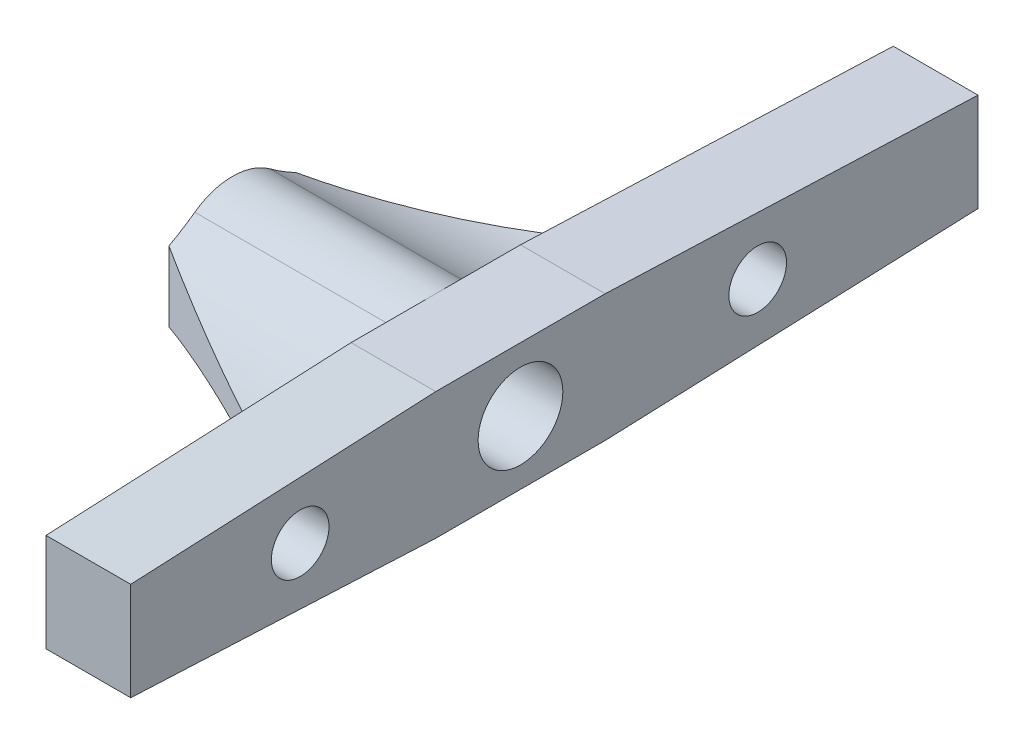
SolidWorks part; units mm, degrees
ref_plane "Front Plane" through (0, 0, 0) normal (0, 0, 1) x (1, 0, 0)
ref_plane "Top Plane" through (0, 0, 0) normal (0, 1, 0) x (1, 0, 0)
ref_plane "Right Plane" through (0, 0, 0) normal (1, 0, 0) x (0, 0, -1)
sketch "Sketch1" plane through (0, 0, 0) normal (1, 0, 0) x (0, 0, -1)
  line L1 (27, -3.75) -> (-23, -3.75)
  line L2 (27, -3.75) -> (27, 3.75)
  line L3 (27, 3.75) -> (-23, 3.75)
  line L4 (-23, -3.75) -> (-23, 3.75)
  line L5 (27, -3.75) -> (-23, 3.75) construction
  line L6 (27, 3.75) -> (-23, -3.75) construction
  circle A0 centre (0, 0) radius 2.5
  point P3 (2, 0)
  dimension "D1" = 5
  dimension "D2" = 7.5
  dimension "D3" = 50
  dimension "D4" = 2
extrude "Boss-Extrude1" add sketch "Sketch1" along normal blind 5
sketch "Sketch2" plane through (0, 0, 0) normal (-1, 0, 0) x (0, 0, 1)
  circle A0 centre (0, 0) radius 3.75
  circle A1 centre (0, 0) radius 2.5
  circle A2 centre (0, 0) radius 2.5 construction
  dimension "D1" = 7.5
extrude "Boss-Extrude2" add sketch "Sketch2" along normal blind 12
sketch "Sketch3" plane through (0, 0, 0) normal (0, 1, 0) x (1, 0, 0)
  line L1 (-12, 3.75) -> (-12, -3.75) construction
  line L2 (0, -4.125) -> (0, 4.125) construction
  line L4 (-12, 3.75) -> (0, 11.15)
  line L5 (0, 11.15) -> (0, 3.15)
  line L6 (0, 3.15) -> (-12, 3.15)
  line L7 (-12, 3.15) -> (-12, 3.75)
  line L12 (-12, -3.15) -> (0, -3.15)
  line L13 (0, -3.15) -> (0, -10.15)
  line L14 (0, -10.15) -> (-12, -3.75)
  line L15 (-12, -3.75) -> (-12, -3.15)
  dimension "D1" = 0.6
  dimension "D2" = 8
  dimension "D3" = 0.6
  dimension "D4" = 7
extrude "Boss-Extrude3" add sketch "Sketch3" along normal blind 0.7 and the other way blind 0.7
chamfer "Chamfer1" [suppressed] distance 18 angle 4
chamfer "Chamfer2" [suppressed] distance 22 angle 4
chamfer "Chamfer3" [suppressed] distance 18 angle 4
chamfer "Chamfer4" [suppressed] distance 22 angle 4
sketch "Sketch4" plane through (0, 0, 0) normal (-1, 0, 0) x (0, 0, 1)
  line L0 (2.75, 0) -> (-2.75, 0) construction
  line L1 (-12.5566, 2.5) -> (-15.4434, 2.5)
  line L2 (-15.4434, 2.5) -> (-16.8868, 0)
  line L3 (-16.8868, 0) -> (-15.4434, -2.5)
  line L4 (-15.4434, -2.5) -> (-12.5566, -2.5)
  line L5 (-12.5566, -2.5) -> (-11.1132, 0)
  line L6 (-11.1132, 0) -> (-12.5566, 2.5)
  line L7 (0, -2.75) -> (0, 2.75) construction
  line L8 (14.4434, 2.5) -> (11.5566, 2.5)
  line L9 (11.5566, 2.5) -> (10.1132, 0)
  line L10 (10.1132, 0) -> (11.5566, -2.5)
  line L11 (11.5566, -2.5) -> (14.4434, -2.5)
  line L12 (14.4434, -2.5) -> (15.8868, 0)
  line L13 (15.8868, 0) -> (14.4434, 2.5)
  circle A0 centre (-14, 0) radius 2.5 construction
  circle A1 centre (13, 0) radius 2.5 construction
  dimension "D1" = 5
  dimension "D2" = 14
  dimension "D3" = 13
extrude "Cut-Extrude1" cut sketch "Sketch4" against normal blind 2
hole_wizard "M3 Clearance Hole1" positions "Sketch6" profile "Sketch7" hole size "M3" standard "ANSI Metric"
sketch "Sketch6" plane through (2, 0, 0) normal (-1, 0, 0) x (0, 0, 1)
  line L0 (2.75, 0) -> (-2.75, 0) construction
  point P0 (-14, 0)
  point P4 (13, 0)
sketch "Sketch7" plane through (2, 0, -14) normal (0, 1, 0) x (0, 0, 1)
  line L0 (0, 0) -> (0, 13.0215)
  line L1 (0, 13.0215) -> (1.7, 12)
  line L2 (1.7, 12) -> (1.7, 0)
  line L5 (1.7, 0) -> (0, 0)
  line L10 (0, 13.0215) -> (-1.7, 12) construction
  line L11 (0, -6.35) -> (0, 107.95) construction
  dimension "Hole Dia." = 3.4
  dimension "Hole Depth" = 12
  dimension "Drill Angle" = 118
fillet "Fillet1" radius 12 4 edges at (-6, -0.7, 3.6841) (-6, -0.7, -3.6841) (-6, 0.7, -3.6841) (-6, 0.7, 3.6841)
sketch "Sketch10" plane through (5, 0, 0) normal (1, 0, 0) x (0, 0, -1)
  line L0 (-23, 2.9) -> (-5, 3.75)
  line L1 (-23, 3.75) -> (-23, -3.75) construction
  line L2 (27, 3.75) -> (-23, 3.75) construction
  line L3 (-5, 3.75) -> (-0.4811, 5.0493)
  line L4 (-0.4811, 5.0493) -> (5, 3.75)
  line L5 (5, 3.75) -> (27, 2.9)
  line L6 (27, -3.75) -> (27, 3.75) construction
  line L7 (-23, 2.9) -> (-23, -2.9)
  line L8 (27, 2.9) -> (27, -2.9)
  line L9 (2.75, 0) -> (-2.75, 0) construction
  line L10 (5, -3.75) -> (27, -2.9)
  line L11 (-0.4811, -5.0493) -> (5, -3.75)
  line L12 (-5, -3.75) -> (-0.4811, -5.0493)
  line L13 (-23, -2.9) -> (-5, -3.75)
  line L15 (-28.1007, 8.3187) -> (30.426, 8.3187)
  line L16 (-28.1007, 8.3187) -> (-28.1007, -8.958)
  line L17 (-28.1007, -8.958) -> (30.426, -8.958)
  line L18 (30.426, 8.3187) -> (30.426, -8.958)
  point P12 (27, 0)
  point P20 (-23, 0)
  dimension "D1" = 18
  dimension "D2" = 22
  dimension "D3" = 5.8
  dimension "D4" = 5.8
extrude "Cut-Extrude2" cut sketch "Sketch10" against normal blind 10
sketch "Sketch11" plane through (5, 0, 0) normal (1, 0, 0) x (0, 0, -1)
  line L1 (-24.609, 4.8639) -> (-20, 4.8639)
  line L2 (-24.609, 4.8639) -> (-24.609, -5.1401)
  line L3 (-24.609, -5.1401) -> (-20, -5.1401)
  line L4 (-20, 4.8639) -> (-20, -5.1401)
  line L5 (20, 4.6495) -> (33.0514, 4.6495)
  line L6 (20, 4.6495) -> (20, -7.248)
  line L7 (20, -7.248) -> (33.0514, -7.248)
  line L8 (33.0514, 4.6495) -> (33.0514, -7.248)
  dimension "D1" = 20
  dimension "D2" = 20
extrude "Cut-Extrude3" [suppressed] cut sketch "Sketch11" against normal blind 10
equation "\"D2@Boss-Extrude3\"=\"D1@Boss-Extrude3\""
